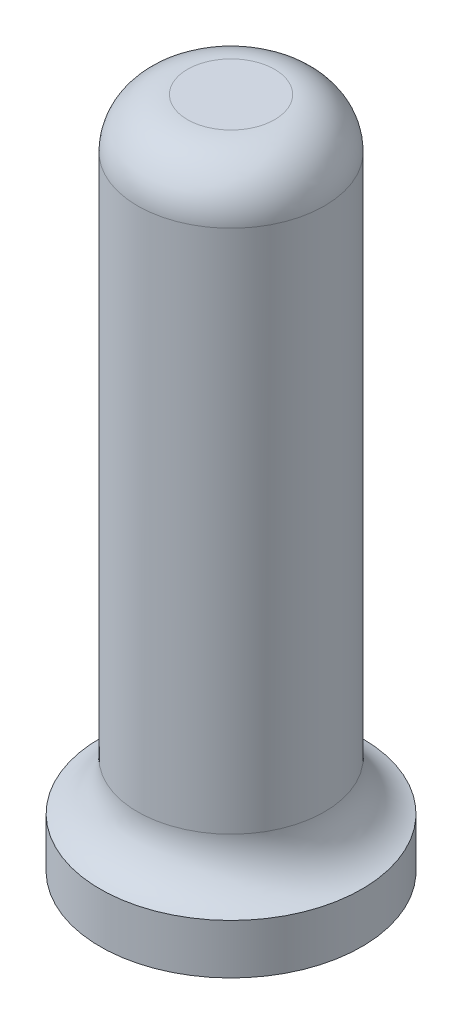
SolidWorks part; units mm, degrees
ref_plane "Front Plane" through (0, 0, 0) normal (0, 0, 1) x (1, 0, 0)
ref_plane "Top Plane" through (0, 0, 0) normal (0, 1, 0) x (1, 0, 0)
ref_plane "Right Plane" through (0, 0, 0) normal (1, 0, 0) x (0, 0, -1)
sketch "Sketch1" plane through (0, 0, 0) normal (0, 1, 0) x (1, 0, 0)
  circle A0 centre (0, 0) radius 3.75
  dimension "D1" = 7.5
extrude "Boss-Extrude1" add sketch "Sketch1" along normal blind 25
fillet "Fillet1" radius 2 1 edges at (0, 25, 3.75)
sketch "Sketch2" plane through (0, 0, 0) normal (0, -1, 0) x (1, 0, 0)
  circle A0 centre (0, 0) radius 5.25
  dimension "D1" = 10.5
extrude "Boss-Extrude2" add sketch "Sketch2" along normal blind 2
fillet "Fillet2" radius 2 1 edges at (0, 0, 3.75)
